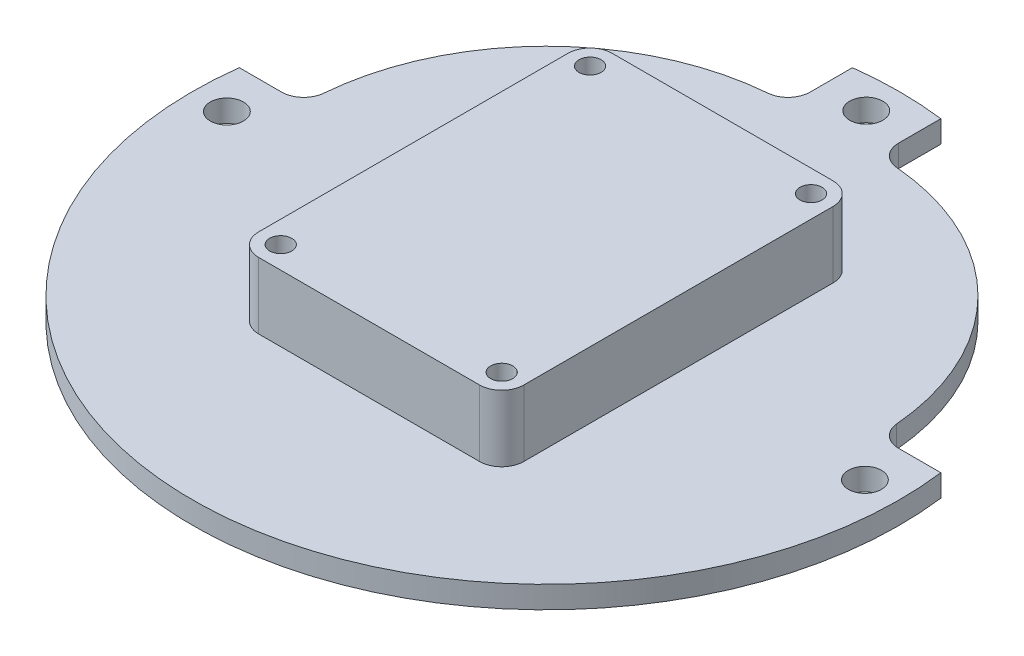
SolidWorks part; units mm, degrees
ref_plane "Front Plane" through (0, 0, 0) normal (0, 0, 1) x (1, 0, 0)
ref_plane "Top Plane" through (0, 0, 0) normal (0, 1, 0) x (1, 0, 0)
ref_plane "Right Plane" through (0, 0, 0) normal (1, 0, 0) x (0, 0, -1)
sketch "Sketch1" plane through (0, 0, 0) normal (0, 1, 0) x (1, 0, 0)
  line L0 (0, -101.6) -> (0, 101.6) construction
  line L1 (-31.75, -50.8) -> (31.75, -50.8)
  line L2 (-38.1, -44.45) -> (-38.1, 44.45)
  line L3 (-31.75, 50.8) -> (31.75, 50.8)
  line L4 (38.1, -44.45) -> (38.1, 44.45)
  line L5 (-38.1, -50.8) -> (38.1, 50.8) construction
  line L6 (-38.1, 50.8) -> (38.1, -50.8) construction
  line L9 (-12.7, 100.8031) -> (-12.7, 88.635)
  line L11 (12.7, 100.8031) -> (12.7, 88.635)
  line L12 (0, 101.6) -> (12.7, 82.55) construction
  line L13 (-12.7, 82.55) -> (0, 101.6) construction
  line L16 (-100.8031, 12.7) -> (-88.635, 12.7)
  line L18 (-101.6, 0) -> (-82.55, 12.7) construction
  line L19 (-101.6, 0) -> (-82.55, -12.7) construction
  line L22 (100.8031, 12.7) -> (88.635, 12.7)
  line L23 (-101.6, 0) -> (101.6, 0) construction
  arc A0 (-100.8031, 12.7) -> (100.8031, 12.7) centre (0, 0) ccw
  arc A1 (-82.307, 18.5208) -> (-18.5208, 82.307) centre (-12.7, 12.7) cw
  arc A2 (18.5208, 82.307) -> (82.307, 18.5208) centre (12.7, 12.7) cw
  circle A3 centre (0, 92.075) radius 4.7625
  circle A4 centre (-91.6766, 0) radius 4.7625
  circle A5 centre (91.6766, 0) radius 4.7625
  arc A6 (12.7, 100.8031) -> (-12.7, 100.8031) centre (0, 0) ccw
  arc A7 (-38.1, -44.45) -> (-31.75, -50.8) centre (-31.75, -44.45) ccw
  arc A8 (31.75, -50.8) -> (38.1, -44.45) centre (31.75, -44.45) ccw
  arc A9 (38.1, 44.45) -> (31.75, 50.8) centre (31.75, 44.45) ccw
  arc A10 (-31.75, 50.8) -> (-38.1, 44.45) centre (-31.75, 44.45) ccw
  circle A11 centre (-31.75, 44.45) radius 3.175
  circle A12 centre (31.75, 44.45) radius 3.175
  circle A13 centre (-31.75, -44.45) radius 3.175
  circle A14 centre (31.75, -44.45) radius 3.175
  arc A15 (82.307, 18.5208) -> (88.635, 12.7) centre (88.635, 19.05) ccw
  arc A16 (12.7, 88.635) -> (18.5208, 82.307) centre (19.05, 88.635) ccw
  arc A17 (-18.5208, 82.307) -> (-12.7, 88.635) centre (-19.05, 88.635) ccw
  arc A18 (-82.307, 18.5208) -> (-88.635, 12.7) centre (-88.635, 19.05) cw
  point P13 (-101.6, 0)
  point P46 (82.55, 12.7)
  dimension "D1" = 203.2
  dimension "D4" = 6.35
  dimension "D5" = 6.35
  dimension "D6" = 6.35
  dimension "D7" = 6.35
  dimension "D8" = 6.35
  dimension "D2" = 76.2
  dimension "D3" = 101.6
extrude "Boss-Extrude1" add sketch "Sketch1" along normal blind 25.4 contours L3 A10 L2 A7 L1 A8 L4 A9 A14 A13 A12 A11 region at (0, 0, 0)
extrude "Boss-Extrude2" add sketch "Sketch1<3>" along normal blind 6.35 contours A1 A18 L16 A0 L22 A15 A2 A16 L11 A6 L9 A17 A5 A4 A3 A10 L3 A9 L4 A8 L1 A7 L2 region at (0, 0, -98.7263)
sketch "Sketch1<3>" plane through (0, 0, 0) normal (0, 1, 0) x (1, 0, 0) same geometry as "Sketch1"
